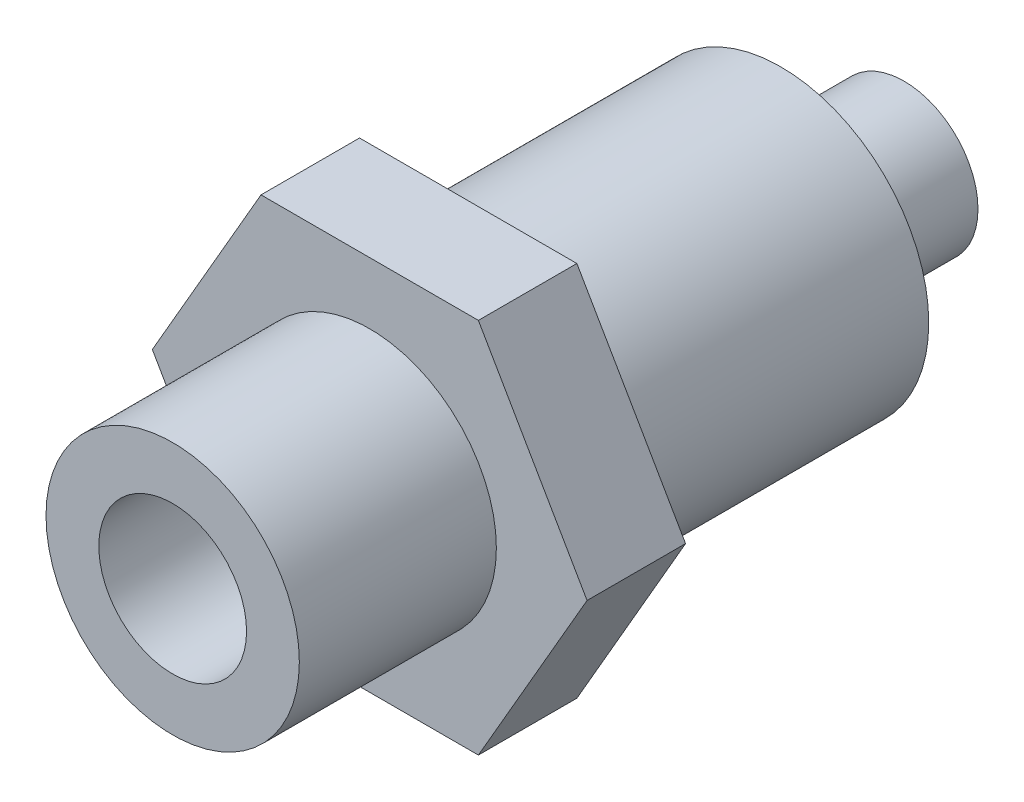
SolidWorks part; units mm, degrees
material "6061-T6 (SS)"
ref_plane "Front Plane" through (0, 0, 0) normal (0, 0, 1) x (1, 0, 0)
ref_plane "Top Plane" through (0, 0, 0) normal (0, 1, 0) x (1, 0, 0)
ref_plane "Right Plane" through (0, 0, 0) normal (1, 0, 0) x (0, 0, -1)
sketch "Sketch1" plane through (0, 0, 0) normal (0, 0, 1) x (1, 0, 0)
  line L0 (55, 0) -> (-55, 0) construction
  line L1 (8.826, 0) -> (4.413, 7.6435)
  line L2 (4.413, 7.6435) -> (-4.413, 7.6435)
  line L3 (-4.413, 7.6435) -> (-8.826, 0)
  line L4 (-8.826, 0) -> (-4.413, -7.6435)
  line L5 (-4.413, -7.6435) -> (4.413, -7.6435)
  line L6 (4.413, -7.6435) -> (8.826, 0)
  circle A0 centre (0, 0) radius 5.1435
  circle A1 centre (0, 0) radius 7.6435 construction
  circle A2 centre (0, 0) radius 3
  circle A3 centre (0, 0) radius 6
  point P14 (5.0398, 8.7291)
  dimension "D1" = 10.287
  dimension "D2" = 2.5
  dimension "D3" = 6
  dimension "D4" = 12
extrude "Boss-Extrude1" add sketch "Sketch1" along normal blind 8 contours A0 A2 region at (-4.998, 0, 0)
extrude "Boss-Extrude2" add sketch "Sketch1<3>" against normal blind 4 separate body contours L5 L6 L1 L2 L3 L4 A0 | A0 A2 | A3 region at (6.4172, -3.705, 0) region at (-4.998, 0, 0)
sketch "Sketch1<3>" plane through (0, 0, 0) normal (0, 0, 1) x (1, 0, 0) same geometry as "Sketch1"
extrude "Boss-Extrude3" add sketch "Sketch1<5>" against normal blind 12.7 from surface contours A3 A0 | A0 A2 | A2 region at (-4.998, 0, 0) region at (0, 0, 0) region at (-5.8303, 0, 0) starting at face at (0, 0, -4)
sketch "Sketch1<5>" plane through (0, 0, 0) normal (0, 0, 1) x (1, 0, 0) same geometry as "Sketch1"
extrude "Boss-Extrude4" add sketch "Sketch1<7>" against normal blind 5 from surface contours A2 starting at face at (6, 0, -16.7)
sketch "Sketch1<7>" plane through (0, 0, 0) normal (0, 0, 1) x (1, 0, 0) same geometry as "Sketch1"
